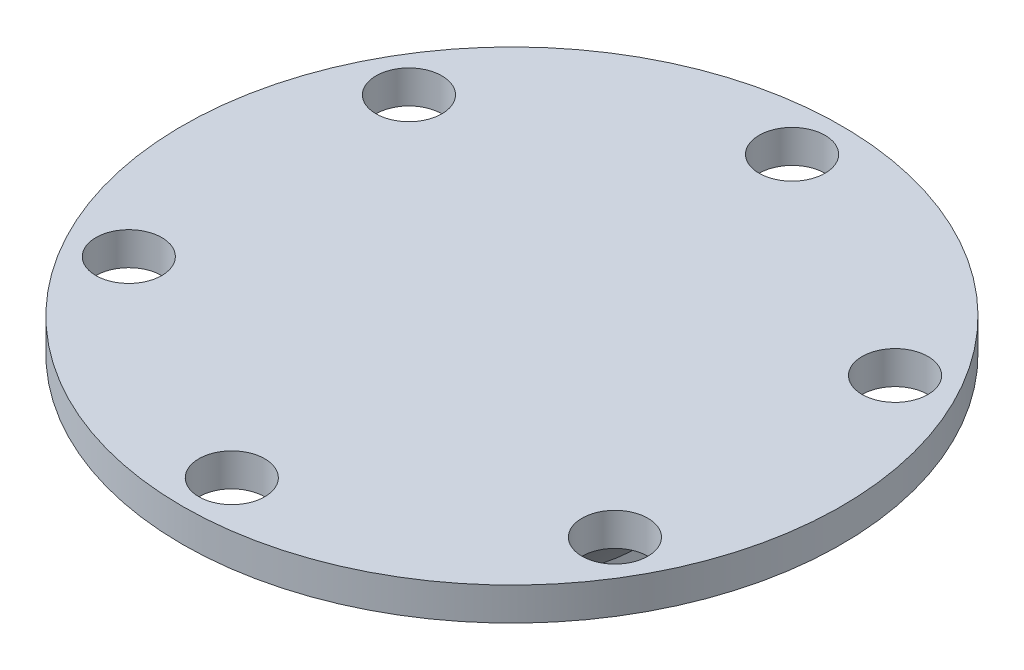
SolidWorks part; units mm, degrees
ref_plane "Front Plane" through (0, 0, 0) normal (0, 0, 1) x (1, 0, 0)
ref_plane "Top Plane" through (0, 0, 0) normal (0, 1, 0) x (1, 0, 0)
ref_plane "Right Plane" through (0, 0, 0) normal (1, 0, 0) x (0, 0, -1)
sketch "Sketch1" plane through (0, 0, 0) normal (0, 1, 0) x (1, 0, 0)
  circle A0 centre (0, 0) radius 127
extrude "Boss-Extrude1" add sketch "Sketch1" along normal blind 12.7
sketch "Sketch2" plane through (0, 12.7, 0) normal (0, 1, 0) x (1, 0, 0)
  circle A0 centre (0, 107.95) radius 12.7
  circle A1 centre (0, -107.95) radius 12.7
  circle A2 centre (93.6625, -53.975) radius 12.7
  circle A3 centre (93.6625, 53.975) radius 12.7
  circle A4 centre (-93.6625, 53.975) radius 12.7
  circle A5 centre (-93.6625, -53.975) radius 12.7
  circle A7 centre (0, 0) radius 127 construction
  point P13 (127, 0)
  dimension "D1" = 107.95
  dimension "D3" = 53.975
  dimension "D4" = 93.6625
  dimension "D5" = 93.6625
  dimension "D6" = 53.975
  dimension "D7" = 93.6625
  dimension "D8" = 53.975
  dimension "D9" = 25.4
  dimension "D10" = 53.975
  dimension "D11" = 93.6625
  dimension "D2" = 107.95
extrude "Cut-Extrude1" cut sketch "Sketch2" against normal blind 12.7
sketch "Sketch3" plane through (0, 0, 0) normal (0, -1, 0) x (-1, 0, 0)
  circle A0 centre (0, 0) radius 88.9
extrude "Boss-Extrude2" add sketch "Sketch3" along normal blind 39.6875
chamfer "Chamfer2" distance 39.6875 1 edges at (0, -39.6875, -88.9)
sketch "Sketch4" plane through (0, -39.6875, 0) normal (0, -1, 0) x (1, 0, 0)
  circle A1 centre (0, 0) radius 49.2125
extrude "Boss-Extrude3" add sketch "Sketch4" along normal blind 4.7625
